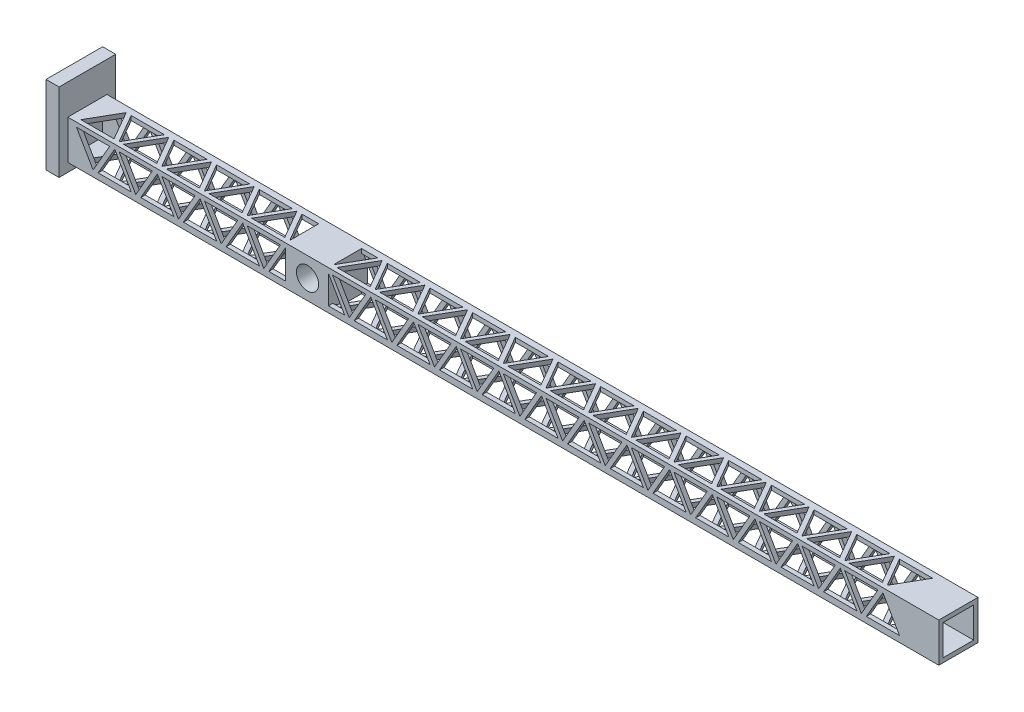
SolidWorks part; units mm, degrees
material "7075-O (SS)"
ref_plane "Front Plane" through (0, 0, 0) normal (0, 0, 1) x (1, 0, 0)
ref_plane "Top Plane" through (0, 0, 0) normal (0, 1, 0) x (1, 0, 0)
ref_plane "Right Plane" through (0, 0, 0) normal (1, 0, 0) x (0, 0, -1)
sketch "Sketch1" plane through (0, 0, 0) normal (0, 1, 0) x (1, 0, 0)
  line L1 (-500, -22.5) -> (500, -22.5)
  line L2 (-500, -22.5) -> (-500, 22.5)
  line L3 (-500, 22.5) -> (500, 22.5)
  line L4 (500, -22.5) -> (500, 22.5)
  line L5 (-500, -22.5) -> (500, 22.5) construction
  line L6 (-500, 22.5) -> (500, -22.5) construction
  point P0 (0, 0)
  dimension "D1" = 1000
  dimension "D2" = 45
extrude "Boss-Extrude1" add sketch "Sketch1" along normal blind 45
sketch "Sketch2" plane through (500, 0, 0) normal (1, 0, 0) x (0, 0, -1)
  line L0 (17.5, 40) -> (-17.5, 40)
  line L1 (-17.5, 40) -> (-17.5, 5)
  line L2 (-17.5, 5) -> (17.5, 5)
  line L3 (17.5, 5) -> (17.5, 40)
  line L4 (-22.5, 0) -> (22.5, 0)
  line L5 (22.5, 0) -> (22.5, 45)
  line L6 (22.5, 45) -> (-22.5, 45)
  line L7 (-22.5, 45) -> (-22.5, 0)
  line L8 (-22.5, 0) -> (22.5, 0)
  line L9 (22.5, 0) -> (22.5, 45)
  line L10 (22.5, 45) -> (-22.5, 45)
  line L11 (-22.5, 45) -> (-22.5, 0)
  dimension "D1" = 0
  dimension "D2" = 5
extrude "Cut-Extrude1" cut sketch "Sketch2" against normal through all contours L0 L1 L2 L3
sketch "Sketch3" plane through (0, 0, 22.5) normal (0, 0, 1) x (1, 0, 0)
  line L1 (-470.9474, 7) -> (-451.8949, 40)
  line L2 (-451.8949, 40) -> (-490, 40)
  line L3 (-490, 40) -> (-470.9474, 7)
  line L4 (-446.1214, 40) -> (-465.1739, 7)
  line L5 (-465.1739, 7) -> (-427.0688, 7)
  line L6 (-427.0688, 7) -> (-446.1214, 40)
  line L9 (-500, 45) -> (-500, 0) construction
  line L11 (-500, 45) -> (500, 45) construction
  circle A0 centre (-470.9474, 29) radius 11 construction
  circle A1 centre (-446.1214, 18) radius 11 construction
  point P14 (0, 0)
  dimension "D1" = 22
  dimension "D2" = 22
  dimension "D3" = 5
  dimension "D4" = 5
  dimension "D6" = 10
extrude "Cut-Extrude2" cut sketch "Sketch3" against normal blind 45
pattern_linear "LPattern1" count 20 spacing 49 along (1, 0, 0) skipping (19, 0) of "Cut-Extrude2"
ref_plane "Plane1" through (0, 22.5, 0) normal (0, 1, 0) x (1, 0, 0)
ref_plane "Plane2" through (0, 0, 0) normal (0, 0, 1) x (1, 0, 0)
ref_axis "Axis1" through (-550, 22.5, 0) along (1, 0, 0)
pattern_circular "CirPattern1" count 2 every 90 about axis through (-550, 22.5, 0) along (1, 0, 0) of "LPattern1"
fillet "Fillet1" [suppressed] radius 2
sketch "Sketch4" plane through (0, 0, 22.5) normal (0, 0, 1) x (1, 0, 0)
  line L0 (-500, 45) -> (500, 45) construction
  line L1 (-249.9842, 45) -> (-200.7386, 45)
  line L2 (-249.9842, 45) -> (-249.9842, 0)
  line L3 (-249.9842, 0) -> (-200.7386, 0)
  line L4 (-200.7386, 45) -> (-200.7386, 0)
  line L5 (-500, 0) -> (500, 0) construction
extrude "Boss-Extrude2" add sketch "Sketch4" against normal up to surface (45 mm away) up to face at (117.0526, 29, -22.5)
sketch "Sketch5" plane through (0, 0, 22.5) normal (0, 0, 1) x (1, 0, 0)
  line L0 (24.75, 22.5) -> (-24.75, 22.5) construction
  line L1 (-550, 22.5) -> (550, 22.5) construction
  circle A0 centre (-224.7463, 22.5) radius 12.75
  dimension "D1" = 25.5
extrude "Cut-Extrude3" cut sketch "Sketch5" against normal blind 50
sketch "Sketch6" plane through (-500, 0, 0) normal (-1, 0, 0) x (0, 0, 1)
  line L0 (-22.5, 45) -> (22.5, 45) construction
  line L1 (22.5, 45) -> (22.5, 0) construction
  line L2 (-22.5, 0) -> (22.5, 0) construction
  line L3 (-22.5, 45) -> (-22.5, 0) construction
  line L4 (-22.5, 45) -> (22.5, 45)
  line L5 (22.5, 45) -> (22.5, 0)
  line L6 (-22.5, 0) -> (22.5, 0)
  line L7 (-22.5, 45) -> (-22.5, 0)
  line L8 (-32.5, 55) -> (32.5, 55)
  line L9 (32.5, 55) -> (32.5, -10)
  line L10 (-32.5, -10) -> (32.5, -10)
  line L11 (-32.5, 55) -> (-32.5, -10)
  line L13 (-32.5, 55) -> (32.5, 55)
  line L14 (-32.5, 55) -> (-32.5, 80)
  line L15 (-32.5, 80) -> (32.5, 80)
  line L16 (32.5, 55) -> (32.5, 80)
  dimension "D2" = 25
  dimension "D1" = 10
extrude "end cap" add sketch "Sketch6" along normal blind 15 separate body contours L8 L9 L10 L11 | L14 L13 L16 L15
